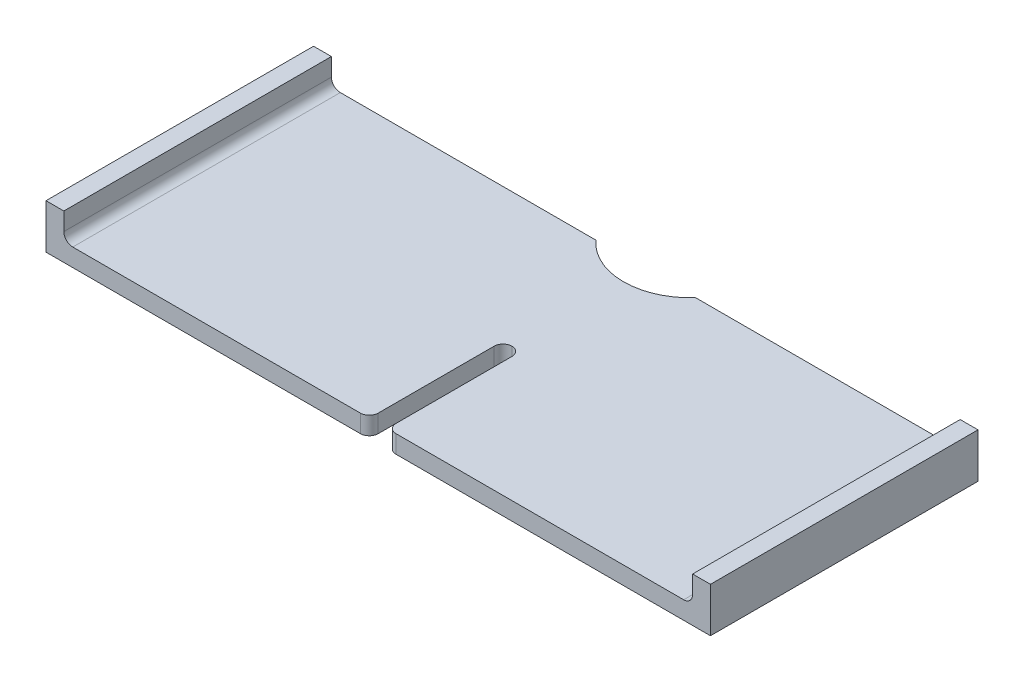
SolidWorks part; units mm, degrees
ref_plane "Front Plane" through (0, 0, 0) normal (0, 0, 1) x (1, 0, 0)
ref_plane "Top Plane" through (0, 0, 0) normal (0, 1, 0) x (1, 0, 0)
ref_plane "Right Plane" through (0, 0, 0) normal (1, 0, 0) x (0, 0, -1)
sketch "Sketch1" plane through (0, 0, 0) normal (0, 1, 0) x (1, 0, 0)
  line L1 (37.25, -15) -> (-37.25, -15)
  line L2 (37.25, -15) -> (37.25, 15)
  line L3 (37.25, 15) -> (-37.25, 15)
  line L4 (-37.25, -15) -> (-37.25, 15)
  line L5 (37.25, -15) -> (-37.25, 15) construction
  line L6 (37.25, 15) -> (-37.25, -15) construction
  point P0 (0, 0)
  dimension "D1" = 74.5
  dimension "D2" = 30
extrude "Boss-Extrude1" add sketch "Sketch1" along normal blind 2
sketch "Sketch4" plane through (0, 0, 0) normal (0, 1, 0) x (1, 0, 0)
  line L0 (0, -25.0714) -> (0, 21.7487) construction
  line L1 (37.25, 15) -> (-37.25, 15) construction
  line L2 (37.25, -15) -> (35.25, -15)
  line L3 (37.25, -15) -> (37.25, 15)
  line L4 (37.25, 15) -> (35.25, 15)
  line L5 (35.25, -15) -> (35.25, 15)
  line L6 (-37.25, 15) -> (-35.25, 15)
  line L7 (-37.25, -15) -> (-37.25, 15)
  line L8 (-37.25, -15) -> (-35.25, -15)
  line L9 (-35.25, -15) -> (-35.25, 15)
  dimension "D1" = 2
extrude "Boss-Extrude2" add sketch "Sketch4" along normal blind 5
sketch "Sketch5" plane through (0, 2, 0) normal (0, 1, 0) x (1, 0, 0)
  line L0 (1, -15) -> (1, 0)
  line L1 (-35.25, -15) -> (35.25, -15) construction
  line L2 (1, 0) -> (-1, 0)
  line L3 (-1, 0) -> (-1, -15)
  line L4 (-1, -15) -> (1, -15)
  point P6 (0, 0)
  dimension "D1" = 2
extrude "Cut-Extrude1" cut sketch "Sketch5" against normal through all both and the other way through all
sketch "Sketch6" plane through (0, 2, 0) normal (0, 1, 0) x (1, 0, 0)
  circle A1 centre (0, 20) radius 7.5
  dimension "D1" = 15
  dimension "D2" = 20
extrude "Cut-Extrude2" cut sketch "Sketch6" against normal through all both and the other way through all
fillet "Fillet1" radius 1 6 edges at (1, 1, 15) (-1, 1, 15) (-1, 1, 0) (1, 1, 0) (-35.25, 2, 0) (35.25, 2, 0)
